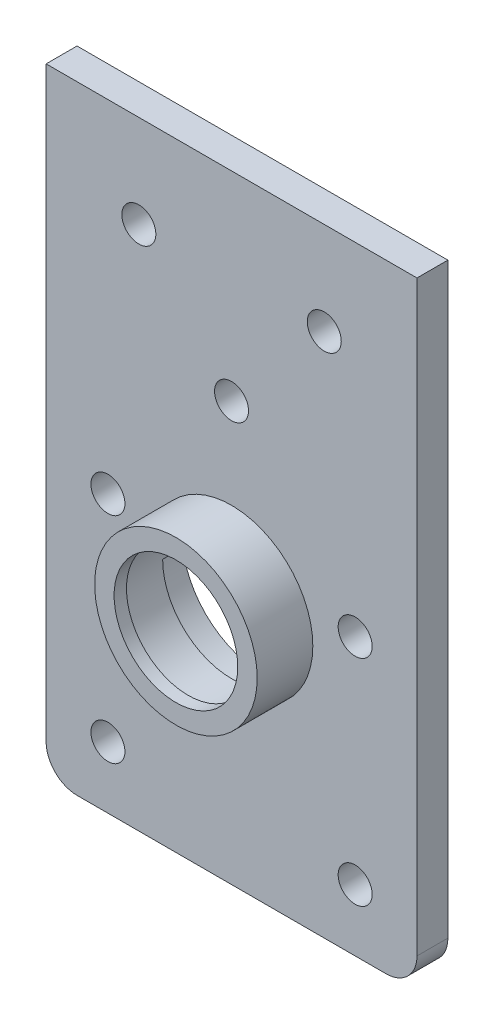
SolidWorks part; units mm, degrees
ref_plane "Front Plane" through (0, 0, 0) normal (0, 0, 1) x (1, 0, 0)
ref_plane "Top Plane" through (0, 0, 0) normal (0, 1, 0) x (1, 0, 0)
ref_plane "Right Plane" through (0, 0, 0) normal (1, 0, 0) x (0, 0, -1)
sketch "Sketch1" plane through (0, 0, 0) normal (0, 0, 1) x (1, 0, 0)
  line L1 (-20, 30) -> (20, 30)
  line L2 (-20, 30) -> (-20, -30)
  line L3 (-20, -30) -> (20, -30)
  line L4 (20, 30) -> (20, -30)
  line L5 (-20, 30) -> (20, -30) construction
  line L6 (-20, -30) -> (20, 30) construction
  point P0 (0, 0)
  dimension "D1" = 40
  dimension "D2" = 60
extrude "Boss-Extrude1" add sketch "Sketch1" along normal blind 5
sketch "Sketch2" plane through (0, 0, 5) normal (0, 0, 1) x (1, 0, 0)
  circle A0 centre (0, 0) radius 11.15
  dimension "D1" = 22.3
extrude "Cut-Extrude1" cut sketch "Sketch2" against normal blind 5
sketch "Sketch3" plane through (0, 0, 5) normal (0, 0, 1) x (1, 0, 0)
  circle A1 centre (0, 0) radius 11.15 construction
  circle A2 centre (0, 0) radius 13.15
  circle A3 centre (0, 0) radius 13.15
  circle A4 centre (0, 0) radius 11.15
  dimension "D1" = 2
extrude "Boss-Extrude2" add sketch "Sketch3" along normal blind 9
sketch "Sketch4" plane through (0, 0, 14) normal (0, 0, 1) x (1, 0, 0)
  circle A0 centre (0, 0) radius 13.15
  circle A1 centre (0, 0) radius 10
  dimension "D1" = 20
extrude "Boss-Extrude3" add sketch "Sketch4" against normal blind 2
sketch "Sketch5" plane through (0, 0, 0) normal (0, 0, -1) x (-1, 0, 0)
  line L0 (0, 0) -> (0, 13.9813)
  line L1 (0, 0) -> (14.18, 0)
  line L2 (0, 0) -> (0, -14.493)
  line L3 (0, 0) -> (-13.7842, 0)
  circle A0 centre (0, 0) radius 11.15 construction
  circle A1 centre (0, 0) radius 11.15
  circle A2 centre (0, 0) radius 13
  circle M2 centre (0, 0) radius 11.15
  dimension "D1" = 26
extrude "Cut-Extrude2" cut sketch "Sketch5" against normal up to surface (5 mm away) contours L1 A2 L0 M2 | L0 A2 L3 M2 | L3 A2 L2 M2 | L2 A2 L1 M2 region at (8.0142, 8.0142, 0) region at (-0.1838, 12.075, 0) region at (-12.075, -0.1838, 0) region at (0.1838, -12.075, 0) up to face at (0, 0, 5)
ref_plane "Plane1" through (0, 0, 2) normal (0, 0, -1) x (-1, 0, 0)
sketch "Sketch7" plane through (0, 0, 5) normal (0, 0, -1) x (-1, 0, 0)
  line L0 (0, 0) -> (13, 0)
  line L1 (0, 0) -> (-13, 0)
  line L2 (0, 0) -> (15.2405, 7.1068)
  line L3 (0, 0) -> (-14.226, -6.6337)
  circle A0 centre (0, 0) radius 13
  circle M6 centre (0, 0) radius 13
  circle M7 centre (0, 0) radius 11.15
  dimension "D1" = 25
  dimension "D2" = 25
extrude "Boss-Extrude4" add sketch "Sketch7" along normal up to surface (5 mm away) contours L3 L1 M7 M6 | L2 L0 M7 M6 region at (-11.7184, 2.5979, 5) region at (11.7184, -2.5979, 5) up to face at (-13, 0, 0)
sketch "Sketch8" plane through (0, 0, 0) normal (0, 0, -1) x (-1, 0, 0)
  line L0 (0, 0) -> (0, 14.8536)
  line L1 (0, 0) -> (0, -15.9502)
  line L2 (0, 0) -> (-13, 0)
  line L3 (-13, 0) -> (13, 0)
  circle A1 centre (0, 0) radius 13
  circle A2 centre (0, 0) radius 11.15
  arc M2 (13, 0) -> (-11.782, -5.494) centre (0, 0) cw
  line M3 (-11.782, -5.494) -> (-10.1053, -4.7122)
  arc M6 (-13, 0) -> (11.782, 5.494) centre (0, 0) cw
  line M7 (11.782, 5.494) -> (10.1053, 4.7122)
extrude "Boss-Extrude5" add sketch "Sketch8" against normal blind 2.5 contours A2 L1 M3 M2 | A2 L0 M7 M6 region at (-6.1576, 9.6654, 0) region at (6.1576, -9.6654, 0)
chamfer "Chamfer1" distance 2 angle 45 2 edges at (0, -12.075, 2.5) (0, 12.075, 2.5)
fillet "Fillet1" radius 5 2 edges at (2, -11.9072, 2.5) (-2, 11.9072, 2.5)
sketch "Sketch10" plane through (0, 0, 5) normal (0, 0, 1) x (1, 0, 0)
  line L4 (-20, -30) -> (20, -30) construction
  line L5 (-20, 30) -> (-20, -30) construction
  line L6 (20, -30) -> (20, 30) construction
  line L7 (20, 30) -> (-20, 30) construction
  line L8 (30, -40) -> (30, 40)
  line L9 (30, 40) -> (-30, 40)
  line L10 (-30, 40) -> (-30, -40)
  line L11 (-30, -40) -> (30, -40)
  line L12 (30, -40) -> (30, 40)
  line L13 (30, 40) -> (-30, 40)
  line L14 (-30, 40) -> (-30, -40)
  line L15 (-30, -40) -> (30, -40)
  line L16 (-20, -30) -> (20, -30)
  line L17 (-20, 30) -> (-20, -30)
  line L18 (20, -30) -> (20, 30)
  line L19 (20, 30) -> (-20, 30)
  dimension "D1" = 10
extrude "Boss-Extrude6" add sketch "Sketch10" against normal up to surface (5 mm away) up to face at (0, 0, 0)
sketch "Sketch11" plane through (0, 0, 0) normal (0, 0, -1) x (-1, 0, 0)
  line L0 (0, -40) -> (0, -20)
  line L1 (-30, -40) -> (30, -40) construction
  line L2 (0, -30) -> (20, -30)
  circle A0 centre (20, -30) radius 2.75
  circle A1 centre (-20, -30) radius 2.75
  dimension "D3" = 5.5
  dimension "D1" = 20
  dimension "D2" = 20
extrude "Cut-Extrude3" cut sketch "Sketch11" against normal blind 10 contours A1 | A0 region at (-20, -32.6722, 0) region at (20, -30, 0)
fillet "Fillet2" radius 5 2 edges at (30, -40, 2.5) (-30, -40, 2.5)
sketch "Sketch12" plane through (0, 0, 5) normal (0, 0, 1) x (1, 0, 0)
  line L0 (-20, 19.75) -> (-20, 4.75)
  line L2 (20, 19.75) -> (20, 4.75)
  line L6 (-15, 19.75) -> (-15, 27.75) construction
  line L7 (15, 27.75) -> (15, 19.75) construction
  circle A0 centre (20, 4.75) radius 2.75
  circle A1 centre (-20, 4.75) radius 2.75
  dimension "D3" = 5.5
  dimension "D4" = 5.5
  dimension "D1" = 15
  dimension "D2" = 15
  dimension "D5" = 5
  dimension "D6" = 5
extrude "Cut-Extrude4" cut sketch "Sketch12" against normal through all both and the other way through all contours A0 | A1 region at (18.1105, 2.8605, 5) region at (-21.8895, 2.8605, 5)
sketch "Sketch14" plane through (0, 40, 0) normal (0, 1, 0) x (1, 0, 0)
  line L4 (30, 0) -> (-30, 0)
  line L5 (-30, 0) -> (-30, -5)
  line L6 (-30, -5) -> (30, -5)
  line L7 (30, -5) -> (30, 0)
  line L8 (30, 0) -> (-30, 0)
  line L9 (-30, 0) -> (-30, -5)
  line L10 (-30, -5) -> (30, -5)
  line L11 (30, -5) -> (30, 0)
  dimension "D1" = 0
extrude "Boss-Extrude7" add sketch "Sketch14" along normal blind 20
sketch "Sketch15" plane through (0, 0, 5) normal (0, 0, 1) x (1, 0, 0)
  line L1 (-30, 60) -> (-15, 60)
  line L2 (-30, 60) -> (-30, 45)
  line L3 (-30, 45) -> (-15, 45)
  line L4 (-15, 60) -> (-15, 45)
  line L5 (30, 60) -> (15, 60)
  line L6 (30, 60) -> (30, 45)
  line L7 (30, 45) -> (15, 45)
  line L8 (15, 60) -> (15, 45)
  circle A0 centre (-15, 45) radius 2.75
  circle A1 centre (15, 45) radius 2.75
  dimension "D5" = 5.5
  dimension "D6" = 5.5
  dimension "D1" = 15
  dimension "D2" = 15
  dimension "D3" = 15
  dimension "D4" = 15
extrude "Cut-Extrude6" cut sketch "Sketch15" against normal blind 20 contours L8 A1 L7 | L7 A1 L8 | L3 A0 L4 | L4 A0 L3 region at (-14.611, 44.611, 5) region at (-16.1671, 46.1671, 5) region at (16.1671, 46.1671, 5) region at (14.611, 44.611, 5)
sketch "Sketch16" plane through (0, 0, 5) normal (0, 0, 1) x (1, 0, 0)
  line L0 (0, 19.75) -> (0, 27.75)
  circle A0 centre (0, 27.75) radius 2.75
  dimension "D2" = 5.5
  dimension "D1" = 8
extrude "Cut-Extrude7" cut sketch "Sketch16" against normal blind 20 contours A0 region at (1.8895, 25.8605, 5)
